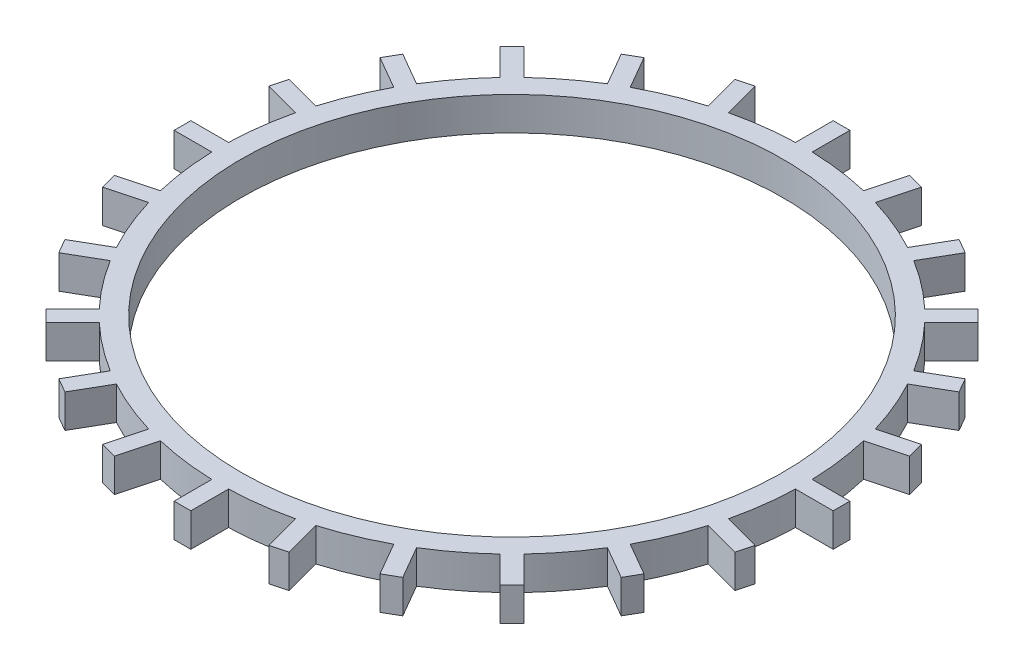
SolidWorks part; units mm, degrees
material "PLA"
ref_plane "Front" through (0, 0, 0) normal (0, 0, 1) x (1, 0, 0)
ref_plane "Top" through (0, 0, 0) normal (0, 1, 0) x (1, 0, 0)
ref_plane "Right" through (0, 0, 0) normal (1, 0, 0) x (0, 0, -1)
other "Configuration Table"
sketch "Esquisse1" plane through (0, 0, 0) normal (0, 1, 0) x (1, 0, 0)
  line L1 (12.2, 0.4) -> (15.8, 0.4)
  line L2 (12.2, 0.4) -> (12.2, -0.4)
  line L3 (12.2, -0.4) -> (15.8, -0.4)
  line L4 (15.8, 0.4) -> (15.8, -0.4)
  line L5 (12.2, 0.4) -> (15.8, -0.4) construction
  line L6 (12.2, -0.4) -> (15.8, 0.4) construction
  circle A0 centre (0, 0) radius 13
  circle A1 centre (0, 0) radius 14
  point P5 (14, 0)
  dimension "D1" = 26
  dimension "D3" = 0.8
  dimension "D4" = 1.8
  dimension "D2" = 1
extrude "Boss.-Extru.1" add sketch "Esquisse1" along normal blind 1.6 contours L1 A1 L3 A0 | L3 A1 L1 A0 region at (-13.3959, 0, 0) region at (13.498, 0, 0)
extrude "Boss.-Extru.2" add sketch "Esquisse1<3>" along normal up to surface (1.6 mm away) contours A1 L3 L4 L1 region at (14.899, 0, 0) up to face at (0, 1.6, 14)
sketch "Esquisse1<3>" plane through (0, 0, 0) normal (0, 1, 0) x (1, 0, 0) same geometry as "Esquisse1"
pattern_circular "Répétition circulaire1" count 24 over 360 about axis through (0, 1.6, 0) along (0, -1, 0) of "Boss.-Extru.2"
